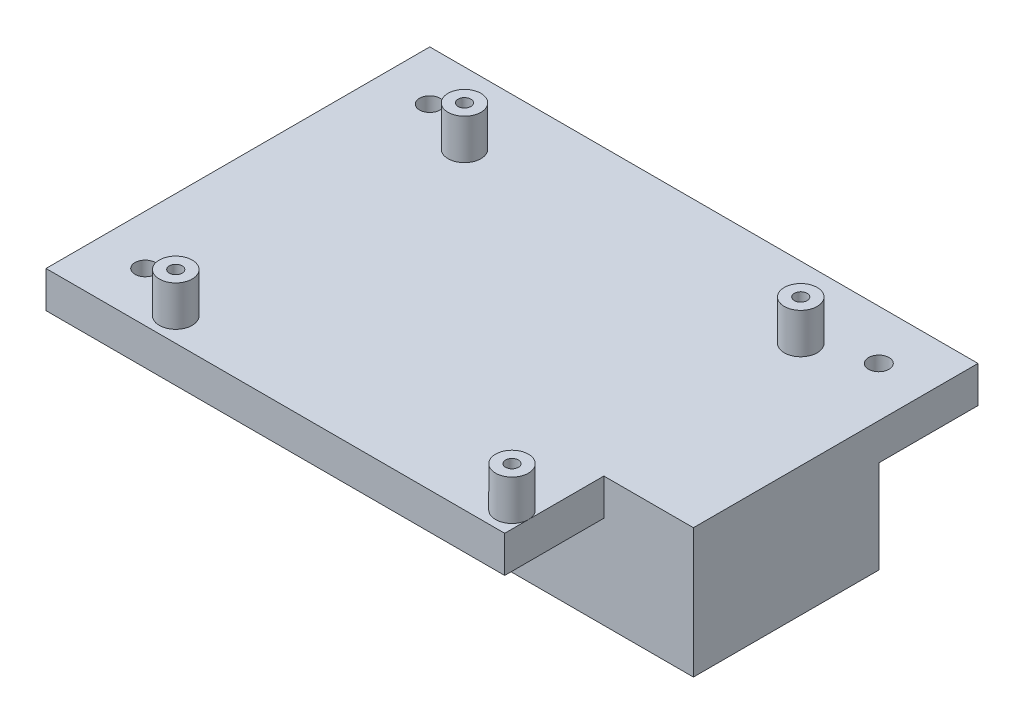
SolidWorks part; units mm, degrees
material "PETG"
ref_plane "Front Plane" through (0, 0, 0) normal (0, 0, 1) x (1, 0, 0)
ref_plane "Top Plane" through (0, 0, 0) normal (0, 1, 0) x (1, 0, 0)
ref_plane "Right Plane" through (0, 0, 0) normal (1, 0, 0) x (0, 0, -1)
sketch "Sketch1" plane through (0, 0, 0) normal (0, 1, 0) x (1, 0, 0)
  line L0 (-61.4313, 38.9312) -> (-61.4313, 52.5) construction
  line L1 (-75, -25.3625) -> (75, -25.3625)
  line L2 (-75, -25.3625) -> (-75, 25.3625)
  line L3 (-75, 25.3625) -> (75, 25.3625)
  line L4 (75, -25.3625) -> (75, 25.3625)
  line L5 (-75, 52.5) -> (75, 52.5)
  line L6 (-75, 52.5) -> (-75, -52.5)
  line L7 (-75, -52.5) -> (75, -52.5)
  line L8 (75, 52.5) -> (75, -52.5)
  line L9 (-61.4313, 38.9312) -> (-75, 38.9312) construction
  line L10 (-61.4313, 38.9312) -> (-61.4313, 25.3625) construction
  line L11 (61.4313, 38.9312) -> (75, 38.9312) construction
  line L13 (-61.4313, -38.9312) -> (-61.4313, -25.3625) construction
  circle A0 centre (-61.4313, 38.9312) radius 2.8
  circle A1 centre (61.4313, 38.9312) radius 2.8
  circle A2 centre (-61.4313, -38.9312) radius 2.8
  circle A3 centre (61.4313, -38.9312) radius 2.8
  point P4 (-75, 0)
  point P5 (0, 25.3625)
  dimension "D4" = 5.6
  dimension "D1" = 50.725
  dimension "D2" = 150
  dimension "D3" = 105
extrude "Boss-Extrude1" add sketch "Sketch1" along normal blind 10 contours L1 L4 L3 L2 | L8 L1 L6 L7 | L8 L5 L6 L3 region at (0, 0, 0) region at (0, 0, 38.9313) region at (0, 0, -38.9312)
extrude "Boss-Extrude2" add sketch "Sketch1<3>" against normal blind 25.4 contours L1 L4 L3 L2 region at (0, 0, 0)
sketch "Sketch1<3>" plane through (0, 0, 0) normal (0, 1, 0) x (1, 0, 0) same geometry as "Sketch1"
sketch "Sketch2" plane through (0, 10, 0) normal (0, 1, 0) x (1, 0, 0)
  line L0 (-46, 33) -> (-46, -46) construction
  line L1 (-46, -46) -> (46, -46) construction
  line L2 (46, -46) -> (46, 33) construction
  line L3 (46, 33) -> (-46, 33) construction
  line L4 (-75, -52.5) -> (75, -52.5) construction
  line L6 (-75, 52.5) -> (75, 52.5) construction
  line L8 (-46, 0) -> (46, 0) construction
  circle A0 centre (-46, 33) radius 4.5
  circle A1 centre (-46, 33) radius 1.75
  circle A2 centre (46, 33) radius 4.5
  circle A3 centre (46, 33) radius 1.75
  circle A4 centre (46, -46) radius 4.5
  circle A5 centre (46, -46) radius 1.75
  circle A6 centre (-46, -46) radius 4.5
  circle A7 centre (-46, -46) radius 1.75
  point P19 (0, 0)
  dimension "D1" = 3.5
  dimension "D2" = 9
  dimension "D3" = 6.5
  dimension "D4" = 92
  dimension "D5" = 19.5
extrude "Boss-Extrude3" add sketch "Sketch2" along normal blind 11
extrude "Cut-Extrude4" cut sketch "Sketch2<3>" against normal up to next contours A1 | A3 | A5 | A7 region at (-46, 10, -33)
sketch "Sketch2<3>" plane through (0, 10, 0) normal (0, 1, 0) x (1, 0, 0) same geometry as "Sketch2"
sketch "Sketch3" plane through (0, 10, 0) normal (0, 1, 0) x (1, 0, 0)
  circle A0 centre (-46, 33) radius 3.2
  circle A1 centre (46, 33) radius 3.2
  circle A2 centre (46, -46) radius 3.2
  circle A3 centre (-46, -46) radius 3.2
  dimension "D1" = 6.4
extrude "Cut-Extrude3" cut sketch "Sketch3" against normal up to next from offset 3.5 offset against normal yes
sketch "Sketch4" plane through (0, 10, 0) normal (0, 1, 0) x (1, 0, 0)
  line L0 (-75, -25.3625) -> (75, -25.3625) construction
  line L1 (75, -52.5) -> (50.5, -52.5)
  line L2 (75, -52.5) -> (75, -25.3625)
  line L3 (75, -25.3625) -> (50.5, -25.3625)
  line L4 (50.5, -52.5) -> (50.5, -25.3625)
  circle A0 centre (46, -46) radius 4.5 construction
extrude "Cut-Extrude5" cut sketch "Sketch4" against normal up to vertex (10 mm away) up to point (75, 0, 25.3625)
equation "\"tol_dia_id_intfc\" = 0.0500mm ' For hole diameters - Interference fit"
equation "\"tol_dia_id_slip\"  = 0.0750mm ' For hole diameters - Slip fit"
equation "\"tol_dia_id_clear\" = 0.1000mm ' For hole diameters - Clearance fit"
equation "\"tol_dia_od_intfc\" = 0.0500mm ' For shaft diameters - Interference fit"
equation "\"tol_dia_od_slip\"  = 0.0750mm ' For shaft diameters - Slip fit"
equation "\"tol_dia_od_clear\" = 0.1000mm ' For shaft diameters - Clearance fit"
equation "\"tol_general_intfc\"= 0.0250mm ' For general parts (Horiz) - Interference fit"
equation "\"tol_general_slip\" = 0.0375mm ' For general parts (Horiz) - Slip fit"
equation "\"tol_general_clear\"= 0.0500mm ' For general parts (Horiz) - Clearance fit"
equation "\"tol_layer_intfc\"  = 0.0250mm ' For all parts (Vert) - Interference fit"
equation "\"tol_layer_slip\"   = 0.0375mm ' For all parts (Vert) - Slip fit"
equation "\"tol_layer_clear\"  = 0.0500mm ' For all parts (Vert) - Clearance fit"
equation "\"tol_corner_rad\"   = 0.100mm ' For corners that fit into other parts"
equation "\"D1@Sketch1\"=50.80mm-\"tol_general_slip\"*2"
